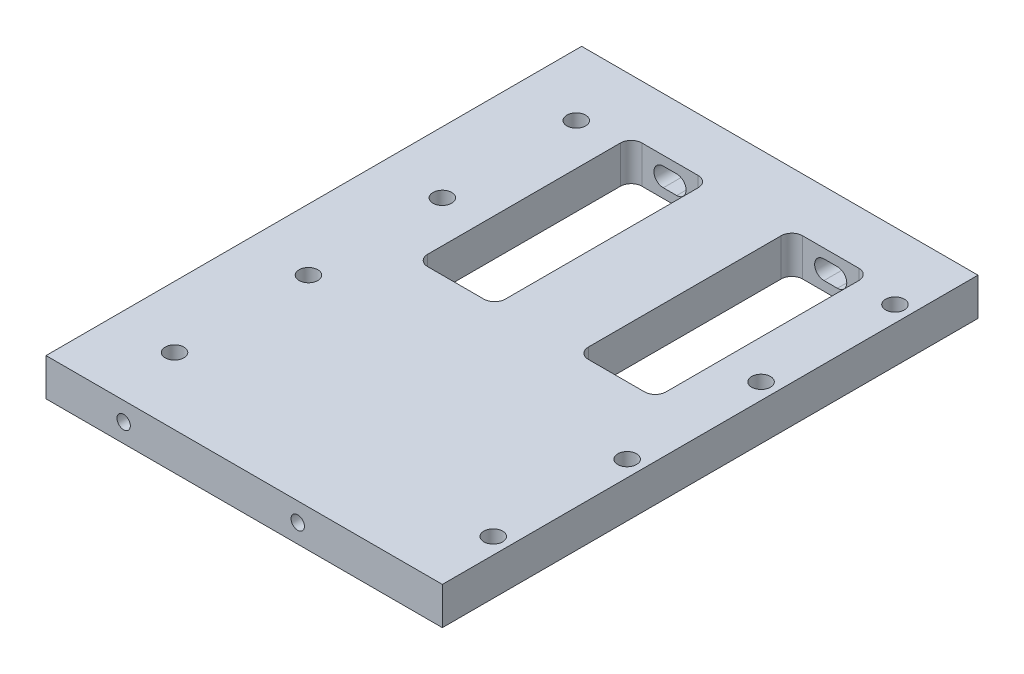
SolidWorks part; units mm, degrees
other "Markup1"
sketch "Sketch11" plane through (-148, 207, 138) normal (-0.4174, 0.5856, 0.6948) x (0.7295, -0.24, 0.6405)
ref_plane "Front Plane" through (0, 0, 0) normal (0, 0, 1) x (1, 0, 0)
ref_plane "Top Plane" through (0, 0, 0) normal (0, 1, 0) x (1, 0, 0)
ref_plane "Right Plane" through (0, 0, 0) normal (1, 0, 0) x (0, 0, -1)
sketch "Sketch1" plane through (0, 0, 0) normal (0, 0, 1) x (1, 0, 0)
  line L1 (-148, 235) -> (-148, 170) construction
  line L4 (-148, 207) -> (-21, 207)
  line L7 (-12, 193) -> (0, 193)
  line L8 (-148, 197.5) -> (-148, 193)
  line L10 (-148, 197.5) -> (-148, 207)
  line L11 (-148, 193) -> (-24, 193)
  line L12 (-12, 207) -> (0, 207)
  line L13 (-148, 207) -> (-21, 207)
  line L16 (-21, 207) -> (-12, 207)
  line L17 (0, 207) -> (0, 193)
  line L18 (-12, 193) -> (-24, 193)
extrude "Boss-Extrude1" add sketch "Sketch1" along normal up to surface (200 mm away) contours L4 L10 L8 L11 region at (-74, 200, 0)
sketch "Sketch3" plane through (0, 207, 0) normal (0, 1, 0) x (1, 0, 0)
  line L4 (-20, -180) -> (-20, -20)
  line L6 (-20, -20) -> (-128, -20)
  line L7 (-42, -20) -> (-107.5, -20)
  line L8 (-107.5, -100) -> (-42, -100)
  line L11 (-42, -20) -> (-39.5, -20)
  line L12 (-128, -20) -> (-128, -180)
  line L15 (-20.5, -20) -> (-20.5, -100)
  line L16 (-39.5, -100) -> (-42, -100)
  line L22 (-109.5, -20) -> (-109.5, -100)
  line L23 (-128, -180) -> (-20, -180)
  line L25 (-39.5, -20) -> (-27.5, -20)
  line L30 (-39.5, -100) -> (-27.5, -100)
  line L31 (-27.5, -20) -> (-22.5, -20)
  line L32 (-27.5, -100) -> (-22.5, -100)
  line L33 (-107.5, -100) -> (-109.5, -100)
  line L34 (-107.5, -20) -> (-109.5, -20)
  line L35 (-22.5, -20) -> (-20.5, -20)
  line L36 (-22.5, -100) -> (-20.5, -100)
  dimension "D1" = 20
extrude "Cut-Extrude1" cut sketch "Sketch3" against normal through all contours L7 region at (-65, 207, 60)
sketch "Sketch14" plane through (0, 0, 0) normal (0, 0, -1) x (-1, 0, 0)
  circle A0 centre (35, 200) radius 4
  circle A1 centre (95, 200) radius 4
hole_wizard "Ø6.0mm Dowel Slot1" positions "Sketch6" profile "Sketch7" size "Ø6.0" standard "ANSI Metric" slot yes end condition through all
sketch "Sketch6" plane through (0, 0, 20) normal (0, 0, 1) x (1, 0, 0)
  line L0 (-116, 200) -> (-104, 200) construction
  line L1 (-101, 200) -> (-89, 200) construction
  point P27 (-95, 200)
  point P32 (-35, 200)
  dimension "D1" = 12
sketch "Sketch7" plane through (-35, 200, 20) normal (1, 0, 0) x (0, -1, 0)
  line L0 (0, 0) -> (0, 20)
  line L1 (0, 20) -> (3.5, 20)
  line L2 (3.5, 20) -> (3.5, 0)
  line L5 (3.5, 0) -> (0, 0)
  line L11 (0, -6.35) -> (0, 107.95) construction
  dimension "Thru Hole Dia." = 7
  dimension "Thru Hole Depth" = 20
sketch "Sketch8" plane through (0, 0, 200) normal (0, 0, 1) x (1, 0, 0)
  line L0 (-48, 200) -> (-54, 200)
  line L2 (-148, 200) -> (-119, 200)
hole_wizard "M6x1.0 Tapped Hole1" positions "Sketch9" profile "Sketch10" tap size "M6x1.0" standard "ANSI Metric"
sketch "Sketch9" plane through (0, 0, 200) normal (0, 0, 1) x (1, 0, 0)
  point P0 (-119, 200)
  point P3 (-54, 200)
sketch "Sketch10" plane through (-119, 200, 200) normal (1, 0, 0) x (0, -1, 0)
  line L0 (0, 0) -> (0, 23)
  line L1 (0, 23) -> (2.5, 21.4978)
  line L2 (2.5, 21.4978) -> (2.5, 0)
  line L5 (2.5, 0) -> (0, 0)
  line L10 (0, 23) -> (-2.5, 21.4978) construction
  line L11 (0, -6.35) -> (0, 107.95) construction
  dimension "Tap Drill Dia." = 5
  dimension "Tap Drill Depth" = 23
  dimension "Drill Angle" = 118
cosmetic thread "Hole Thread1" parameters "D1"=20, "D2"=6
cosmetic thread "Hole Thread2" parameters "D1"=20, "D2"=6
fillet "Fillet1" radius 4 4 edges at (-20.5, 200, 20) (-20.5, 200, 100) (-109.5, 200, 100) (-109.5, 200, 20)
sketch "Sketch15" plane through (0, 0, 20) normal (0, 0, 1) x (1, 0, 0)
  line L1 (-80.5, 200) -> (-80.5, 193)
  line L2 (-105.5, 193) -> (-24.5, 193) construction
  line L4 (-49.5, 200) -> (-49.5, 193)
  line L5 (-49.5, 193) -> (-80.5, 193)
  line L6 (-80.5, 200) -> (-80.5, 207)
  line L7 (-105.5, 207) -> (-24.5, 207) construction
  line L8 (-80.5, 207) -> (-49.5, 207)
  line L9 (-49.5, 207) -> (-49.5, 200)
extrude "Boss-Extrude2" add sketch "Sketch15" along normal up to surface (80 mm away) up to face at (-65, 200, 100)
fillet "Fillet2" radius 4 4 edges at (-49.5, 200, 100) (-49.5, 200, 20) (-80.5, 200, 100) (-80.5, 200, 20)
sketch "Sketch13" plane through (0, 193, 0) normal (0, -1, 0) x (1, 0, 0)
  circle A0 centre (-6, 25) radius 3.5
  circle A1 centre (-6, 75) radius 3.5
  circle A2 centre (-6, 75) radius 3.5
  circle A3 centre (-6, 125) radius 3.5
  circle A4 centre (-6, 175) radius 3.5
  circle A5 centre (-125, 175) radius 3.5
  circle A6 centre (-125, 125) radius 3.5
  circle A7 centre (-125, 75) radius 3.5
  circle A8 centre (-125, 25) radius 3.5
extrude "Cut-Extrude2" cut sketch "Sketch13" against normal through all contours A1 | A3 | A4 | A6 | A7 | A0 | A5 | A8 region at (-6, 193, 75) region at (-6, 193, 125) region at (-6, 193, 175) region at (-125, 193, 125) region at (-125, 193, 75)
